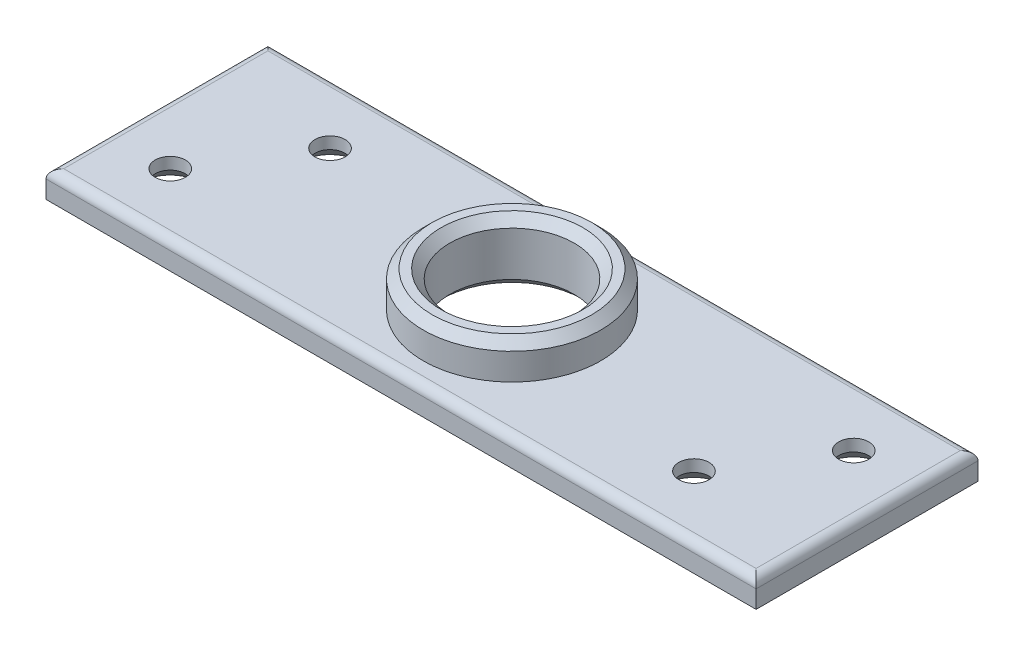
SolidWorks part; units mm, degrees
material "Aço cromo inoxidável"
ref_plane "Plano frontal" through (0, 0, 0) normal (0, 0, 1) x (1, 0, 0)
ref_plane "Plano superior" through (0, 0, 0) normal (0, 1, 0) x (1, 0, 0)
ref_plane "Plano direito" through (0, 0, 0) normal (1, 0, 0) x (0, 0, -1)
other "Caixa delimitadora"
ref_plane "Default Plane" through (-40, -1.5, 12.5) normal (0, 0, -1) x (-1, 0, 0)
sketch "Esboço1" plane through (0, 0, 0) normal (0, 1, 0) x (1, 0, 0)
  line L1 (-40, -12.5) -> (40, -12.5)
  line L2 (-40, -12.5) -> (-40, 12.5)
  line L3 (-40, 12.5) -> (40, 12.5)
  line L4 (40, -12.5) -> (40, 12.5)
  line L5 (-40, -12.5) -> (40, 12.5) construction
  line L6 (-40, 12.5) -> (40, -12.5) construction
  circle A0 centre (0, 0) radius 10
  point P0 (0, 0)
  dimension "D3" = 20
  dimension "D1" = 80
  dimension "D2" = 25
extrude "Ressalto-extrusão1" add sketch "Esboço1" along normal mid plane 3
sketch "Esboço2" plane through (0, -1.5, 0) normal (0, -1, 0) x (1, 0, 0)
  circle A0 centre (0, 0) radius 10 construction
  circle A1 centre (0, 0) radius 10
  circle A2 centre (0, 0) radius 7
  dimension "D1" = 3
extrude "Ressalto-extrusão2" add sketch "Esboço2" against normal offset from surface (7 mm away) 4 separate body up to face at (0, 1.5, 0) offset beyond the face yes
chamfer "Chanfro1" distance 1 angle 45 4 edges at (0, 5.5, -7) (0, 5.5, -10) (0, -1.5, -10) (0, -1.5, -7)
fillet "Filete1" radius 1 4 edges at (-40, 1.5, 0) (0, 1.5, -12.5) (40, 1.5, 0) (0, 1.5, 12.5)
sketch "Esboço3" plane through (0, -1.5, 0) normal (0, -1, 0) x (-1, 0, 0)
  point P0 (26, 5.5)
  point P1 (33, -5.5)
  point P3 (-26, -5.5)
  point P5 (-33, 5.5)
  dimension "D1" = 26
  dimension "D2" = 33
  dimension "D3" = 26
  dimension "D4" = 33
  dimension "D5" = 5.5
  dimension "D6" = 5.5
hole_wizard "Escareado para SFHCS M31" positions "Esboço4" profile "Esboço5" countersink size "M3" standard "Ansi Metric" end condition through all
sketch "Esboço4" plane through (0, -1.5, 0) normal (0, -1, 0) x (-1, 0, 0)
  point P0 (-33, 5.5)
  point P3 (-26, -5.5)
  point P6 (26, 5.5)
  point P9 (33, -5.5)
sketch "Esboço5" plane through (33, -1.5, -5.5) normal (1, 0, 0) x (0, 0, -1)
  line L0 (0, 0) -> (0, 7)
  line L1 (0, 7) -> (1.7, 7)
  line L2 (1.7, 7) -> (1.7, 1.66)
  line L3 (1.7, 1.66) -> (3.36, 0)
  line L5 (3.36, 0) -> (0, 0)
  line L6 (-1.7, 1.66) -> (-3.36, 0) construction
  line L11 (0, -6.35) -> (0, 107.95) construction
  dimension "Thru Hole Dia." = 3.4
  dimension "Thru Hole Depth" = 7
  dimension "Near C'Sink Dia." = 6.72
  dimension "Near C'Sink Angle" = 90
